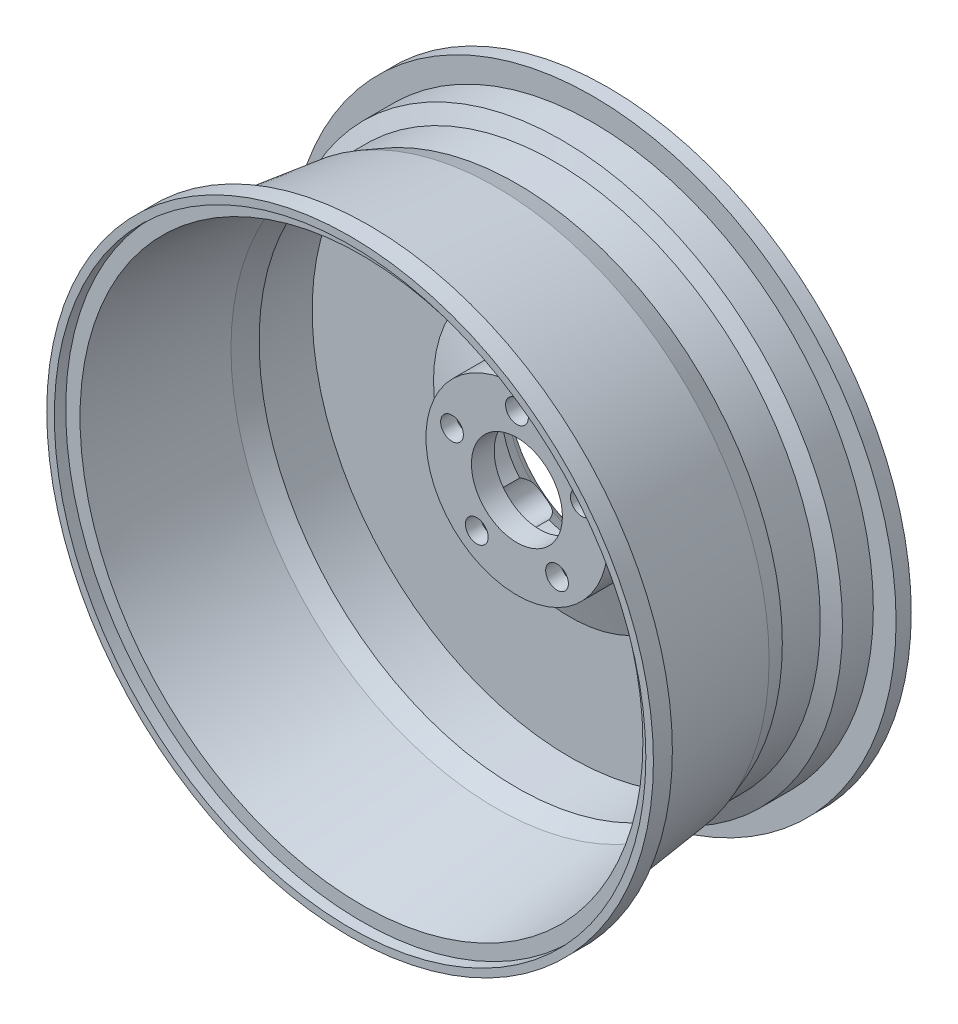
SolidWorks part; units mm, degrees
material "4032-T6"
ref_plane "Front Plane" through (0, 0, 0) normal (0, 0, 1) x (1, 0, 0)
ref_plane "Top Plane" through (0, 0, 0) normal (0, 1, 0) x (1, 0, 0)
ref_plane "Right Plane" through (0, 0, 0) normal (1, 0, 0) x (0, 0, -1)
sketch "Sketch1" plane through (0, 0, 0) normal (1, 0, 0) x (0, 0, -1)
  line L0 (0, 0) -> (0, 241.3) construction
  line L1 (31.75, 38.1) -> (50.8, 38.1)
  line L3 (0, 0) -> (171.9647, 0) construction
  line L4 (31.75, 38.1) -> (31.75, 76.2)
  line L5 (31.75, 76.2) -> (63.5, 76.2)
  line L6 (82.55, 63.5) -> (93.1478, 69.6187)
  line L7 (76.2, 215.9) -> (31.75, 215.9)
  line L8 (31.75, 215.9) -> (14.4879, 222.1829)
  line L9 (14.4879, 222.1829) -> (-98.425, 235.663)
  line L10 (-98.425, 235.663) -> (-98.425, 247.65)
  line L11 (-98.425, 247.65) -> (-107.95, 247.65)
  line L12 (-107.95, 247.65) -> (-107.95, 254)
  line L13 (-107.95, 254) -> (-92.075, 254)
  line L14 (-92.075, 254) -> (-92.075, 241.3)
  line L15 (-92.075, 241.3) -> (14.3035, 228.6)
  line L16 (14.3035, 228.6) -> (31.75, 222.25)
  line L17 (31.75, 222.25) -> (63.5, 222.25)
  line L18 (63.5, 222.25) -> (69.4221, 234.95)
  line L19 (69.4221, 234.95) -> (95.25, 234.95)
  line L20 (95.25, 234.95) -> (95.25, 254)
  line L21 (95.25, 254) -> (107.95, 254)
  line L22 (107.95, 254) -> (107.95, 247.65)
  line L23 (107.95, 247.65) -> (101.6, 247.65)
  line L24 (101.6, 247.65) -> (101.6, 228.6)
  line L25 (101.6, 228.6) -> (88.9, 228.6)
  line L26 (63.5, 76.2) -> (76.2, 114.3)
  line L27 (76.2, 114.3) -> (76.2, 215.9)
  line L28 (82.55, 63.5) -> (50.8, 63.5)
  line L29 (88.9, 215.9) -> (88.9, 228.6)
  line L30 (50.8, 63.5) -> (50.8, 38.1)
  line L31 (105.6083, 95.0956) -> (88.9, 215.9)
  arc A0 (93.1478, 69.6187) -> (105.6083, 95.0956) centre (80.4478, 91.6157) ccw
  point P33 (107.95, 78.1647)
  dimension "D32" = 25.4
  dimension "D2" = 241.3
  dimension "D3" = 228.6
  dimension "D4" = 6.35
  dimension "D5" = 6.35
  dimension "D6" = 38.1
  dimension "D7" = 38.1
  dimension "D8" = 31.75
  dimension "D9" = 31.75
  dimension "D10" = 107.95
  dimension "D11" = 115
  dimension "D12" = 6.35
  dimension "D13" = 31.75
  dimension "D14" = 63.5
  dimension "D15" = 19.05
  dimension "D16" = 12.7
  dimension "D17" = 6.35
  dimension "D18" = 107.95
  dimension "D19" = 6.35
  dimension "D20" = 6.35
  dimension "D21" = 6.35
  dimension "D22" = 9.525
  dimension "D23" = 30
  dimension "D24" = 12.7
  dimension "D25" = 160
  dimension "D26" = 12.7
  dimension "D27" = 14.4879
  dimension "D28" = 76.2
  dimension "D29" = 101.6
  dimension "D30" = 31.75
  dimension "D31" = 6.35
  dimension "D33" = 19.05
revolve "Revolve1" add sketch "Sketch1" angle 360 about L3
sketch "Sketch2" plane through (0, 0, -50.8) normal (0, 0, -1) x (-1, 0, 0)
  circle A0 centre (0, 57.15) radius 9.525
  circle A1 centre (0, 0) radius 57.15 construction
  circle A2 centre (54.3529, 17.6603) radius 9.525
  circle A3 centre (33.5919, -46.2353) radius 9.525
  circle A4 centre (-33.5919, -46.2353) radius 9.525
  circle A5 centre (-54.3529, 17.6603) radius 9.525
  dimension "D1" = 19.05
  dimension "D2" = 114.3
  dimension "D3" = 5
extrude "Cut-Extrude1" cut sketch "Sketch2" against normal through all and the other way through all
sketch "Sketch3" plane through (0, 0, -50.8) normal (0, 0, -1) x (-1, 0, 0)
  circle A0 centre (0, 57.15) radius 15.875
  circle A1 centre (0, 0) radius 57.15 construction
  circle A2 centre (54.3536, 17.6613) radius 15.875
  circle A3 centre (33.5937, -46.2347) radius 15.875
  circle A4 centre (-33.5901, -46.2359) radius 15.875
  circle A5 centre (-54.3522, 17.6594) radius 15.875
  dimension "D2" = 31.75
  dimension "D1" = 5
extrude "Cut-Extrude2" cut sketch "Sketch3" along normal through all
chamfer "Chamfer1" distance 6.35 angle 45 5 edges at (63.8779, 17.6603, -50.8) (43.1169, -46.2353, -50.8) (-24.0669, -46.2353, -50.8) (-44.8279, 17.6603, -50.8) (9.525, 57.15, -50.8)
